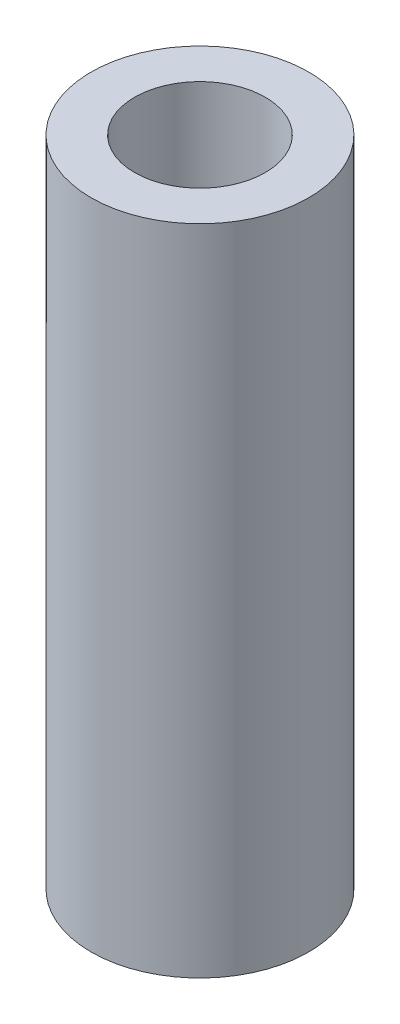
SolidWorks part; units mm, degrees
ref_plane "Front Plane" through (0, 0, 0) normal (0, 0, 1) x (1, 0, 0)
ref_plane "Top Plane" through (0, 0, 0) normal (0, 1, 0) x (1, 0, 0)
ref_plane "Right Plane" through (0, 0, 0) normal (1, 0, 0) x (0, 0, -1)
sketch "Sketch1" plane through (0, 0, 0) normal (0, 1, 0) x (1, 0, 0)
  circle A0 centre (0, 0) radius 2.5
  circle A1 centre (0, 0) radius 1.5
  dimension "D1" = 3
  dimension "D2" = 1
extrude "Boss-Extrude1" add sketch "Sketch1" along normal blind 15 contours A0 A1 region at (-2.4293, 0, 0)
equation "\"TABH\"=3"
equation "\"D1@Sketch1\"=\"TABH\""
equation "\"T\"=1"
equation "\"D2@Sketch1\"=\"T\""
